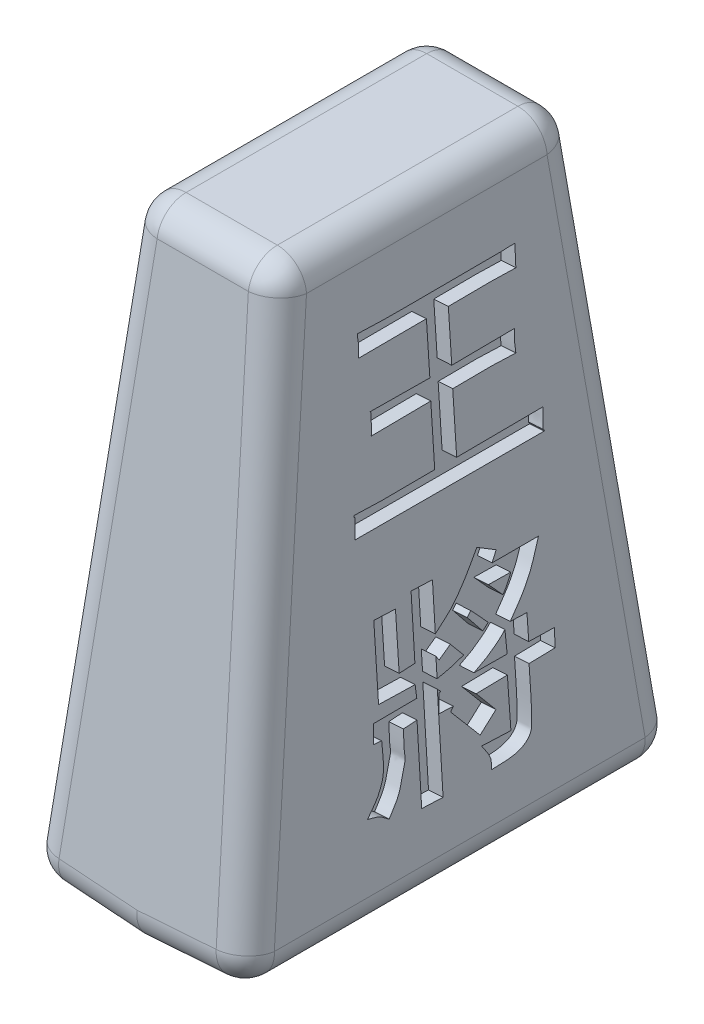
SolidWorks part; units mm, degrees
ref_plane "Płaszczyzna przednia" through (0, 0, 0) normal (0, 0, 1) x (1, 0, 0)
ref_plane "Płaszczyzna górna" through (0, 0, 0) normal (0, 1, 0) x (1, 0, 0)
ref_plane "Płaszczyzna prawa" through (0, 0, 0) normal (1, 0, 0) x (0, 0, -1)
sketch "Szkic1" plane through (0, 0, 0) normal (0, 0, 1) x (1, 0, 0)
  line L0 (0, 0) -> (0, 40)
  line L1 (3.1225, 40) -> (-3.1225, 40)
  line L2 (-5.1185, 38.1262) -> (-7.3738, 2.4704)
  line L3 (-5.504, 0.3481) -> (0, 0)
  line L4 (5.504, 0.3481) -> (0, 0)
  line L5 (5.1185, 38.1262) -> (7.3738, 2.4704)
  arc A0 (-3.1225, 40) -> (-5.1185, 38.1262) centre (-3.1225, 38) ccw
  arc A1 (-7.3738, 2.4704) -> (-5.504, 0.3481) centre (-5.3777, 2.3441) ccw
  arc A2 (7.3738, 2.4704) -> (5.504, 0.3481) centre (5.3777, 2.3441) cw
  arc A3 (3.1225, 40) -> (5.1185, 38.1262) centre (3.1225, 38) cw
  point P7 (-5, 40)
  point P10 (-7.5, 0.4744)
  point P17 (7.5, 0.4744)
  point P18 (5, 40)
  dimension "D5" = 2
  dimension "D1" = 40
  dimension "D2" = 90
  dimension "D3" = 5
  dimension "D4" = 7.5
extrude "Dodanie-wyciągnięcie1" add sketch "Szkic1" along normal blind 30 contours L2 A1 L3 L0 L1 A0 | A3 L1 L0 L4 A2 L5 region at (-3.1441, 18.7866, 0) region at (3.1441, 18.7866, 0)
ref_plane "Płaszczyzna1" through (5.1225, 0, 0) normal (1, 0, 0) x (0, 0, -1)
ref_plane "Płaszczyzna2" through (15.1225, 0, 0) normal (1, 0, 0) x (0, 0, -1)
sketch "Szkic7" plane through (15.1225, 0, 0) normal (1, 0, 0) x (0, 0, -1)
  line L0 (-25, 40) -> (-5, 40)
  line L1 (-30, 40) -> (0, 40) construction
  line L2 (-5, 40) -> (0, 0)
  line L3 (0, 0) -> (-30, 0)
  line L4 (-30, 0) -> (0, 0) construction
  line L5 (-15, 0) -> (-15, 40)
  line L6 (-25, 40) -> (-30, 0)
  line L8 (0, 0) -> (-30, 0)
  line L9 (0, 0) -> (0, 40)
  line L10 (0, 40) -> (-30, 40)
  line L11 (-30, 0) -> (-30, 40)
  dimension "D1" = 10
  dimension "D2" = 15
  dimension "D3" = 40
extrude "Wytnij-wyciągnięcie11" cut sketch "Szkic7" against normal through all and the other way through all contours L11 L6 L10 | L9 L10 L2 region at (15.1225, 26.6667, 28.3333) region at (15.1225, 26.6667, 1.6667)
fillet "Zaokrąglenie2" radius 2 18 edges at (0, 40, 5) (-4.4914, 39.4582, 4.9323) (-6.2461, 20.2983, 2.5373) (-6.8784, 1.022, 0.1278) (-2.752, 0.1741, 0.0218) (2.752, 0.1741, 0.0218) (6.8784, 1.022, 0.1278) (6.2461, 20.2983, 2.5373) (4.4914, 39.4582, 4.9323) (4.4914, 39.4582, 25.0677) (6.2461, 20.2983, 27.4627) (6.8784, 1.022, 29.8722) (2.752, 0.1741, 29.9782) (-2.752, 0.1741, 29.9782) (-6.8784, 1.022, 29.8722) (-6.2461, 20.2983, 27.4627) (-4.4914, 39.4582, 25.0677) (0, 40, 25)
sketch "Szkic10" plane through (7.5, 0.4744, 0) normal (0.998, 0.0631, 0) x (0, 0, -1)
  line L0 (341.3333, 1024) -> (1706.6667, 1024) construction
  line L1 (-9.2168, 33.8142) -> (-9.2368, 32.4142)
  line L2 (-13.8568, 32.4342) -> (-13.8368, 29.0342)
  line L3 (-13.8368, 29.0342) -> (-9.5368, 29.0742)
  line L4 (-13.8568, 27.6942) -> (-13.8368, 23.7342)
  line L5 (-13.8368, 23.7342) -> (-7.9168, 23.7742)
  line L6 (-7.9168, 22.4142) -> (-7.9368, 22.3742)
  line L7 (-7.9368, 22.3742) -> (-20.8768, 22.3942)
  line L8 (-20.8768, 23.7142) -> (-20.8568, 23.7942)
  line L9 (-15.3368, 23.7542) -> (-15.3568, 27.7142)
  line L10 (-15.3568, 27.7142) -> (-19.4368, 27.6742)
  line L11 (-19.4368, 29.0742) -> (-15.3368, 29.0342)
  line L12 (-15.3368, 29.0342) -> (-15.3568, 32.4542)
  line L13 (-15.3568, 32.4542) -> (-19.9968, 32.4342)
  line L14 (-10.0568, 24.8742) -> (-11.2768, 23.8942)
  line L15 (-12.8168, 18.0542) -> (-11.5368, 17.2942)
  line L16 (-11.5368, 17.2942) -> (-11.8568, 16.6942)
  line L17 (-11.8568, 16.6942) -> (-8.6768, 16.6942)
  line L18 (-10.8568, 12.8342) -> (-9.7168, 12.7942)
  line L19 (-9.7168, 12.7942) -> (-9.6968, 11.1142)
  line L20 (-9.6968, 11.1142) -> (-7.9368, 11.0742)
  line L21 (-7.9368, 11.0742) -> (-7.9768, 9.9142)
  line L22 (-7.9768, 9.9142) -> (-9.7568, 9.8742)
  line L23 (-13.1968, 6.7942) -> (-11.1968, 6.7142)
  line L24 (-11.1968, 6.7142) -> (-11.2368, 9.9342)
  line L25 (-11.2368, 9.9342) -> (-13.3768, 9.8942)
  line L26 (-13.3768, 9.8942) -> (-12.1168, 8.3742)
  line L27 (-12.1168, 8.3742) -> (-13.2568, 7.4542)
  line L28 (-13.2568, 7.4542) -> (-15.1368, 9.6942)
  line L29 (-15.1368, 9.6942) -> (-14.9368, 9.9342)
  line L30 (-14.9368, 9.9342) -> (-15.9168, 9.9742)
  line L31 (-15.9168, 9.9742) -> (-15.8568, 11.1342)
  line L32 (-15.8568, 11.1342) -> (-15.7168, 11.1742)
  line L33 (-15.7168, 11.1742) -> (-15.9368, 11.3942)
  line L34 (-15.9368, 11.3942) -> (-15.9368, 5.1742)
  line L35 (-15.9368, 5.1742) -> (-17.3968, 5.2342)
  line L36 (-17.3968, 5.2342) -> (-17.3968, 10.3342)
  line L37 (-17.3968, 10.3342) -> (-18.3368, 10.2742)
  line L38 (-19.8168, 10.3142) -> (-20.3768, 10.3542)
  line L39 (-20.3768, 10.3542) -> (-20.3168, 11.5342)
  line L40 (-20.3168, 11.5342) -> (-17.3368, 11.5542)
  line L41 (-17.3368, 11.5542) -> (-17.3968, 12.3742)
  line L42 (-17.3968, 12.3742) -> (-19.8968, 12.4342)
  line L43 (-19.8968, 12.4342) -> (-19.9168, 17.2942)
  line L44 (-19.9168, 17.2942) -> (-18.4368, 17.2342)
  line L45 (-18.4368, 17.2342) -> (-18.4168, 13.5142)
  line L46 (-18.4168, 13.5142) -> (-17.3368, 13.5742)
  line L47 (-17.3368, 13.5742) -> (-17.3368, 17.7342)
  line L48 (-17.3368, 17.7342) -> (-15.8768, 17.6742)
  line L49 (-15.8768, 17.6742) -> (-15.8768, 14.5542)
  line L50 (-12.1768, 15.5942) -> (-10.6568, 15.5742)
  line L51 (-11.2568, 14.5742) -> (-12.1768, 15.5942)
  line L52 (-13.4368, 14.7142) -> (-12.3168, 13.4942)
  line L53 (-12.3168, 13.4942) -> (-12.7168, 13.1942)
  line L54 (-12.7168, 13.1942) -> (-13.6968, 14.4342)
  line L55 (-13.6968, 14.4342) -> (-13.4368, 14.7142)
  line L56 (-14.9168, 13.4942) -> (-14.0768, 12.4742)
  line L57 (-15.9168, 11.9942) -> (-15.9168, 13.2942)
  line L58 (-15.9168, 13.2942) -> (-15.7168, 12.9742)
  line L59 (-15.7168, 12.9742) -> (-14.9168, 13.4942)
  line L60 (-11.2368, 12.5542) -> (-11.1768, 11.1142)
  line L61 (-11.1768, 11.1142) -> (-13.4368, 11.1342)
  spline S0 degree 3 poles (-19.9968, 33.8342) (-19.2901, 33.8142) (-18.5837, 33.777) (-17.8768, 33.7742) (-15.2102, 33.7636) (-12.5434, 33.7809) (-9.8768, 33.7942) (-9.8674, 33.7942) (-9.8662, 33.8139) (-9.8568, 33.8142) (-9.6436, 33.8206) (-9.4301, 33.8142) (-9.2168, 33.8142) knots 0 0 0 0 1 1 1 2 2 2 3 3 3 4 4 4 4
  spline S1 degree 3 poles (-9.2368, 32.4142) (-9.8101, 32.4275) (-10.3833, 32.4517) (-10.9568, 32.4542) (-11.9235, 32.4584) (-12.8901, 32.4408) (-13.8568, 32.4342) knots 0 0 0 0 1 1 1 2 2 2 2
  spline S2 degree 3 poles (-9.5368, 29.0742) (-9.5501, 28.7942) (-9.5768, 28.5145) (-9.5768, 28.2342) (-9.5768, 28.0404) (-9.5501, 27.8475) (-9.5368, 27.6542) knots 0 0 0 0 1 1 1 2 2 2 2
  spline S3 degree 3 poles (-9.5368, 27.6542) (-10.1367, 27.6782) (-10.7365, 27.7142) (-11.3368, 27.7142) (-12.1768, 27.7142) (-13.0168, 27.7008) (-13.8568, 27.6942) knots 0 0 0 0 1 1 1 2 2 2 2
  spline S4 degree 3 poles (-7.9168, 23.7742) (-7.9301, 23.5808) (-7.9539, 23.3879) (-7.9568, 23.1942) (-7.9678, 22.456) (-8.1148, 22.6122) (-7.9168, 22.4142) knots 0 0 0 0 1 1 1 2 2 2 2
  spline S5 degree 3 poles (-20.8768, 22.3942) (-20.8635, 22.5875) (-20.8398, 22.7804) (-20.8368, 22.9742) (-20.8261, 23.6726) (-20.6883, 23.5256) (-20.8768, 23.7142) knots 0 0 0 0 1 1 1 2 2 2 2
  spline S6 degree 3 poles (-20.8568, 23.7942) (-20.2301, 23.7742) (-19.6038, 23.7387) (-18.9768, 23.7342) (-17.7635, 23.7254) (-16.5501, 23.7475) (-15.3368, 23.7542) knots 0 0 0 0 1 1 1 2 2 2 2
  spline S7 degree 3 poles (-19.4368, 27.6742) (-19.3961, 27.9183) (-19.3845, 28.1668) (-19.3768, 28.4142) (-19.3765, 28.4236) (-19.3962, 28.4248) (-19.3968, 28.4342) (-19.4374, 29.0839) (-19.2697, 28.907) (-19.4368, 29.0742) knots 0 0 0 0 1 1 1 2 2 2 3 3 3 3
  spline S8 degree 3 poles (-19.9968, 32.4342) (-19.9835, 32.7342) (-19.9633, 33.0339) (-19.9568, 33.3342) (-19.9566, 33.3436) (-19.9761, 33.3448) (-19.9768, 33.3542) (-19.9896, 33.5138) (-19.9901, 33.6742) (-19.9968, 33.8342) knots 0 0 0 0 1 1 1 2 2 2 3 3 3 3
  spline S9 degree 3 poles (-12.5168, 27.5742) (-12.4968, 27.5675) (-12.4727, 27.568) (-12.4568, 27.5542) (-12.3499, 27.4615) (-12.2551, 27.3558) (-12.1568, 27.2542) (-11.424, 26.4961) (-10.6908, 25.7195) (-10.0568, 24.8742) knots 0 0 0 0 1 1 1 2 2 2 3 3 3 3
  spline S10 degree 3 poles (-11.2768, 23.8942) (-11.2968, 23.9008) (-11.3219, 23.8993) (-11.3368, 23.9142) (-11.3708, 23.9482) (-11.3889, 23.995) (-11.4168, 24.0342) (-11.5554, 24.2282) (-11.7226, 24.4119) (-11.8768, 24.5942) (-12.4202, 25.2364) (-12.9941, 25.8472) (-13.5768, 26.4542) knots 0 0 0 0 1 1 1 2 2 2 3 3 3 4 4 4 4
  spline S11 degree 3 poles (-13.5768, 26.4542) (-13.5701, 26.4742) (-13.5704, 26.4981) (-13.5568, 26.5142) (-13.4959, 26.5861) (-13.4228, 26.6469) (-13.3568, 26.7142) (-13.0762, 27.0002) (-12.7968, 27.2875) (-12.5168, 27.5742) knots 0 0 0 0 1 1 1 2 2 2 3 3 3 3
  spline S12 degree 3 poles (-8.6768, 16.6942) (-8.9301, 16.0742) (-9.1259, 15.4274) (-9.4368, 14.8342) (-9.8163, 14.11) (-10.3403, 13.468) (-10.8568, 12.8342) knots 0 0 0 0 1 1 1 2 2 2 2
  spline S13 degree 3 poles (-9.7568, 9.8742) (-9.7768, 8.6608) (-9.6816, 7.4401) (-9.8168, 6.2342) (-9.8452, 5.9806) (-10.0342, 5.7493) (-10.2368, 5.5942) (-10.4816, 5.4068) (-10.7937, 5.3102) (-11.0968, 5.2542) (-11.5961, 5.1619) (-12.1101, 5.1875) (-12.6168, 5.1542) knots 0 0 0 0 1 1 1 2 2 2 3 3 3 4 4 4 4
  spline S14 degree 3 poles (-12.6168, 5.1542) (-12.6301, 5.3942) (-12.5767, 5.6476) (-12.6568, 5.8742) (-12.7754, 6.2094) (-13.0168, 6.4875) (-13.1968, 6.7942) knots 0 0 0 0 1 1 1 2 2 2 2
  spline S15 degree 3 poles (-18.3368, 10.2742) (-18.4176, 8.1531) (-18.1953, 8.8387) (-18.4368, 8.1142) (-18.5901, 7.6542) (-18.6872, 7.1714) (-18.8968, 6.7342) (-19.0774, 6.3573) (-19.3635, 6.0408) (-19.5968, 5.6942) knots 0 0 0 0 1 1 1 2 2 2 3 3 3 3
  spline S16 degree 3 poles (-19.5968, 5.6942) (-19.8101, 5.8408) (-20.0027, 6.0236) (-20.2368, 6.1342) (-20.4886, 6.2531) (-20.7701, 6.2942) (-21.0368, 6.3742) knots 0 0 0 0 1 1 1 2 2 2 2
  spline S17 degree 3 poles (-21.0368, 6.3742) (-20.7701, 6.7075) (-20.4512, 7.0051) (-20.2368, 7.3742) (-20.0396, 7.7135) (-19.8723, 8.0856) (-19.8168, 8.4742) (-19.7301, 9.0813) (-19.8168, 9.7008) (-19.8168, 10.3142) knots 0 0 0 0 1 1 1 2 2 2 3 3 3 3
  spline S18 degree 3 poles (-15.8768, 14.5542) (-15.4235, 14.9342) (-14.9146, 15.2563) (-14.5168, 15.6942) (-13.8649, 16.4118) (-13.3373, 17.2362) (-12.8168, 18.0542) knots 0 0 0 0 1 1 1 2 2 2 2
  spline S19 degree 3 poles (-10.6568, 15.5742) (-10.7021, 15.4157) (-10.772, 15.3026) (-10.8568, 15.1542) (-10.9047, 15.0704) (-10.9424, 14.9919) (-10.9968, 14.9142) (-11.0396, 14.8531) (-11.18, 14.6126) (-11.2568, 14.5742) knots 0 0 0 0 1 1 1 2 2 2 3 3 3 3
  spline S20 degree 3 poles (-14.0768, 12.4742) (-14.0835, 12.4675) (-14.0879, 12.4572) (-14.0968, 12.4542) (-14.2822, 12.3903) (-14.4689, 12.3301) (-14.6568, 12.2742) (-14.8676, 12.2114) (-15.0814, 12.1585) (-15.2968, 12.1142) (-15.5006, 12.0722) (-15.7137, 12.045) (-15.9168, 11.9942) knots 0 0 0 0 1 1 1 2 2 2 3 3 3 4 4 4 4
  spline S21 degree 3 poles (-13.4368, 11.1342) (-13.4301, 11.1408) (-13.4253, 11.1501) (-13.4168, 11.1542) (-13.1403, 11.2851) (-12.9052, 11.3921) (-12.6368, 11.5342) (-12.5494, 11.5805) (-12.4618, 11.6431) (-12.3768, 11.6942) (-11.9702, 11.9381) (-11.5742, 12.2168) (-11.2368, 12.5542) knots 0 0 0 0 1 1 1 2 2 2 3 3 3 4 4 4 4
  point P85 (0, 0)
extrude "Wytnij-wyciągnięcie12" cut sketch "Szkic10" against normal blind 1 contours S8 L13 L12 L11 S7 L10 L9 S6 L8 S5 L7 L6 S4 L5 L4 S3 S2 L3 L2 S1 L1 S0 | S18 L49 L48 L47 L46 L45 L44 L43 L42 L41 L40 L39 L38 S17 S16 S15 L37 L36 L35 L34 L33 L32 L31 L30 L29 L28 L27 L26 L25 L24 L23 S14 S13 L22 L21 L20 L19 L18 S12 L17 L16 L15 L54 L55 L52 L53 L50 S19 L51 region at (5.74, 28.3005, 14.532) region at (6.767, 12.0631, 14.5821)
